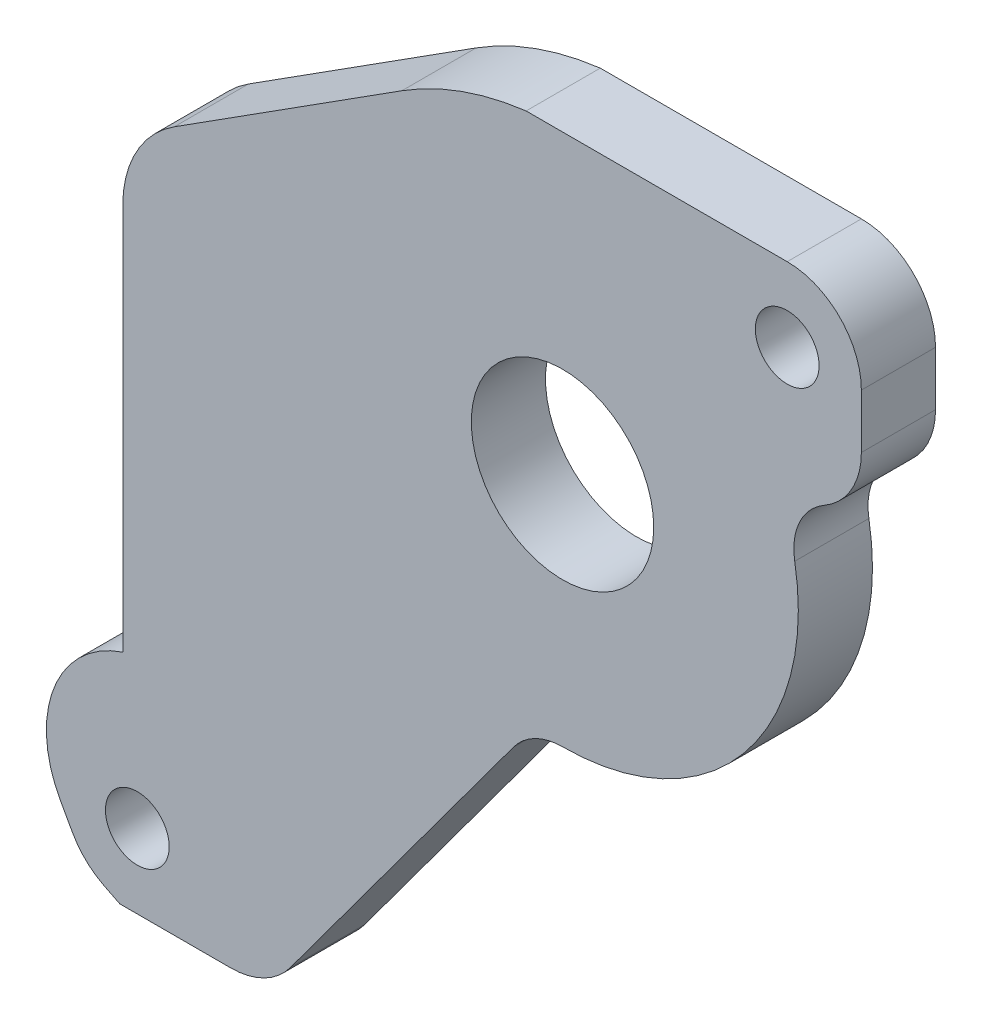
SolidWorks part; units mm, degrees
material "ﾎﾟﾘｴﾁﾚﾝｲﾐﾝ(PEI)"
ref_plane "正面" through (0, 0, 0) normal (0, 0, 1) x (1, 0, 0)
ref_plane "平面" through (0, 0, 0) normal (0, 1, 0) x (1, 0, 0)
ref_plane "右側面" through (0, 0, 0) normal (1, 0, 0) x (0, 0, -1)
sketch "ｽｹｯﾁ1" plane through (0, 0, 0) normal (0, 0, 1) x (1, 0, 0)
  line L0 (0, 24.75) -> (0, -24.75) construction
  line L1 (-5, 24.75) -> (5, 24.75) construction
  line L2 (-5, 24.75) -> (-5, -24.75) construction
  line L3 (-5, -24.75) -> (5, -24.75) construction
  line L4 (5, 24.75) -> (5, -24.75) construction
  line L5 (-5, 24.75) -> (5, -24.75) construction
  line L6 (-5, -24.75) -> (5, 24.75) construction
  line L7 (-5, 0) -> (5, 0) construction
  line L8 (0.65, -27.15) -> (0.65, -20.15)
  line L9 (-10.15, 20.15) -> (10.15, 20.15)
  line L10 (-10.15, 20.15) -> (-10.15, -20.15)
  line L11 (-10.15, -20.15) -> (10.15, -20.15)
  line L12 (10.15, 20.15) -> (10.15, -20.15)
  line L13 (-10.15, 20.15) -> (10.15, -20.15) construction
  line L14 (-10.15, -20.15) -> (10.15, 20.15) construction
  line L15 (-0.65, 27.15) -> (0.65, 27.15)
  line L16 (-0.65, 27.15) -> (-0.65, 20.15)
  line L17 (-0.65, 20.15) -> (0.65, 20.15)
  line L18 (0.65, 27.15) -> (0.65, 20.15)
  line L19 (-0.65, 27.15) -> (0.65, 20.15) construction
  line L20 (-0.65, 20.15) -> (0.65, 27.15) construction
  line L21 (-0.65, -27.15) -> (-0.65, -20.15)
  line L22 (-0.65, -27.15) -> (0.65, -27.15)
  line L23 (10.15, 0) -> (-51.75, 0) construction
  line L25 (-59.85, 30) -> (20.15, 30)
  line L26 (-59.85, 30) -> (-59.85, -30)
  line L27 (-59.85, -30) -> (20.15, -30)
  line L28 (20.15, 30) -> (20.15, -30)
  line L29 (-59.85, 30) -> (20.15, -30) construction
  line L30 (-59.85, -30) -> (20.15, 30) construction
  circle A0 centre (-5, 24.75) radius 2.15
  circle A1 centre (5, 24.75) radius 2.15
  circle A2 centre (5, -24.75) radius 2.15
  circle A3 centre (-5, -24.75) radius 2.15
  circle A4 centre (0, 10) radius 6.15
  point P0 (0, 0)
  point P14 (0, 0)
  point P19 (0, 23.65)
  point P29 (-19.85, 0)
  dimension "D3" = 4.3
  dimension "D11" = 12.3
  dimension "D1" = 10
  dimension "D2" = 49.5
  dimension "D4" = 20.3
  dimension "D5" = 40.3
  dimension "D6" = 1.3
  dimension "D7" = 7
  dimension "D8" = 60
  dimension "D9" = 10
  dimension "D10" = 80
  dimension "D12" = 20
extrude "ﾎﾞｽ - 押し出し1" add sketch "ｽｹｯﾁ1" along normal blind 5 contours L28 L25 L26 L27 A1 A0 L22 L21 L11 L10 L9 L16 L15 L18 L12 L8 A2 A3 | L12 L9 L10 L11 | A3 | L21 L22 L8 L11 | A2 | A0 | A1 | L18 L15 L16 L9 region at (0, -23.65, 0) region at (0, -1.6992, 0) region at (0, 23.65, 0) region at (-24.3956, 0, 0) region at (-5, 24.75, 0) region at (5, 24.75, 0) region at (5, -24.75, 0) region at (-5, -24.75, 0)
sketch "ｽｹｯﾁ2" plane through (0, 0, 5) normal (0, 0, 1) x (1, 0, 0)
  line L0 (-59.85, 0) -> (20.15, 0) construction
  line L1 (-59.85, 30) -> (-59.85, -30) construction
  line L2 (20.15, 30) -> (20.15, -30) construction
  line L3 (-54.85, 0) -> (-54.85, 10) construction
  line L4 (-54.85, 10) -> (-34.85, 10) construction
  circle A0 centre (-54.85, 10) radius 2.15
  circle A1 centre (-54.85, -10) radius 2.15
  circle A2 centre (-34.85, 10) radius 2.15
  circle A3 centre (-34.85, -10) radius 2.15
  dimension "D1" = 4.3
  dimension "D2" = 5
  dimension "D3" = 20
  dimension "D5" = 20
  dimension "D4" = 2
extrude "ｶｯﾄ - 押し出し1" cut sketch "ｽｹｯﾁ2" against normal through all
sketch "ｽｹｯﾁ3" plane through (0, 0, 5) normal (0, 0, 1) x (1, 0, 0)
  line L0 (-59.85, 30) -> (20.15, 30) construction
  line L1 (20.15, 30) -> (20.15, -30) construction
  line L6 (20.15, -30) -> (20.15, 30)
  line L7 (20.15, 30) -> (-59.85, 30)
  line L8 (-59.85, 30) -> (-59.85, -30)
  line L9 (-59.85, -30) -> (20.15, -30)
  line L10 (20.15, -30) -> (20.15, 30)
  line L11 (20.15, 30) -> (-59.85, 30)
  line L12 (-59.85, 30) -> (-59.85, -30)
  line L13 (-59.85, -30) -> (20.15, -30)
  circle A0 centre (15.15, 25) radius 5
  circle A1 centre (15.15, 25) radius 2.15
  line M12 (20.15, 30) -> (-59.85, 30)
  dimension "D1" = 10
  dimension "D2" = 4.3
  dimension "D3" = 0
extrude "ｶｯﾄ - 押し出し2" cut sketch "ｽｹｯﾁ3" against normal through all contours A1 | A0 L10 M12 region at (19.0332, 28.8832, 5) region at (15.15, 25, 5)
sketch "ｽｹｯﾁ4" plane through (0, 0, 5) normal (0, 0, 1) x (1, 0, 0)
  line L0 (-59.85, 0) -> (20.15, 0) construction
  line L1 (-59.85, 30) -> (-59.85, -30) construction
  line L2 (20.15, 25) -> (20.15, -30) construction
  line L3 (-59.85, 15) -> (-29.85, 30)
  line L4 (-59.85, 30) -> (15.15, 30) construction
  line L5 (-59.85, -15) -> (-29.85, -30)
  line L6 (12.0657, -6.1382) -> (-19.85, -30)
  line L10 (20.15, -30) -> (20.15, 25)
  line L11 (15.15, 30) -> (-59.85, 30)
  line L12 (-59.85, 30) -> (-59.85, -30)
  line L13 (-59.85, -30) -> (20.15, -30)
  line L14 (20.15, -30) -> (20.15, 25)
  line L15 (15.15, 30) -> (-59.85, 30)
  line L16 (-59.85, 30) -> (-59.85, -30)
  line L17 (-59.85, -30) -> (20.15, -30)
  circle A0 centre (0, 10) radius 6.15 construction
  arc A1 (20.15, 25) -> (15.15, 30) centre (15.15, 25) ccw
  arc A2 (20.15, 25) -> (15.15, 30) centre (15.15, 25) ccw
  circle A3 centre (0, 10) radius 6.15
  circle A4 centre (0, 10) radius 20.15
  line M15 (20.15, -30) -> (20.15, 25)
  line M17 (15.15, 30) -> (-59.85, 30)
  line M18 (-59.85, 30) -> (-59.85, -30)
  line M19 (-59.85, -30) -> (20.15, -30)
  dimension "D4" = 40
  dimension "D1" = 30
  dimension "D2" = 30
  dimension "D3" = 0
extrude "ｶｯﾄ - 押し出し3" cut sketch "ｽｹｯﾁ4" against normal through all contours L3 M18 M17 | L5 M18 M19 | L0 A4 L6 M19 M15 | A4 L0 L14 region at (-49.85, 25, 5) region at (-49.85, -25, 5) region at (19.3629, 2.4658, 5) region at (6.9241, -19.8416, 5)
sketch "ｽｹｯﾁ6" plane through (0, 0, 5) normal (0, 0, 1) x (1, 0, 0)
  line L0 (-59.85, -15) -> (-29.85, -30) construction
  line L1 (-29.85, -30) -> (-19.85, -30) construction
  circle A0 centre (-28.6697, -25) radius 5 construction
  circle A1 centre (-28.6697, -25) radius 2.15
  dimension "D1" = 10
  dimension "D2" = 4.3
extrude "ｶｯﾄ - 押し出し5" cut sketch "ｽｹｯﾁ6" against normal through all
sketch "ｽｹｯﾁ7" plane through (0, 0, 5) normal (0, 0, 1) x (1, 0, 0)
  line L0 (-39.85, -15.2) -> (-33.038, -27.4326)
  line L1 (-34.85, 10) -> (-34.85, -10) construction
  line L2 (-39.85, -15.2) -> (-29.65, -15.2)
  line L3 (-39.85, 15) -> (-29.85, 15) construction
  line L4 (-39.85, 15) -> (-39.85, -15) construction
  line L5 (-39.85, -15) -> (-29.85, -15) construction
  line L6 (-29.85, 15) -> (-29.85, -15) construction
  line L7 (-39.85, 15) -> (-29.85, -15) construction
  line L8 (-39.85, -15) -> (-29.85, 15) construction
  line L9 (-29.65, 15) -> (-29.65, -15.2)
  line L10 (-29.65, 15) -> (-10.8282, 26.9933)
  line L17 (-29.85, 30) -> (-59.85, 15)
  line L18 (-59.85, 15) -> (-59.85, -15)
  line L19 (-59.85, -15) -> (-29.85, -30)
  line L20 (-29.85, -30) -> (-19.85, -30)
  line L21 (-19.85, -30) -> (12.0657, -6.1382)
  line L22 (20.15, 10) -> (20.15, 25)
  line L23 (15.15, 30) -> (-29.85, 30)
  line L24 (-29.85, 30) -> (-59.85, 15)
  line L25 (-59.85, 15) -> (-59.85, -15)
  line L26 (-59.85, -15) -> (-29.85, -30)
  line L27 (-29.85, -30) -> (-19.85, -30)
  line L28 (-19.85, -30) -> (12.0657, -6.1382)
  line L29 (20.15, 10) -> (20.15, 25)
  line L30 (15.15, 30) -> (-29.85, 30)
  circle A1 centre (-34.85, -10) radius 2.15 construction
  circle A2 centre (15.15, 25) radius 5
  arc A3 (20.15, 25) -> (15.15, 30) centre (15.15, 25) ccw construction
  circle A4 centre (-28.6697, -25) radius 5
  circle A5 centre (0, 10) radius 20.15
  arc A6 (12.0657, -6.1382) -> (20.15, 10) centre (0, 10) ccw
  arc A7 (20.15, 25) -> (15.15, 30) centre (15.15, 25) ccw
  arc A8 (12.0657, -6.1382) -> (20.15, 10) centre (0, 10) ccw
  arc A9 (20.15, 25) -> (15.15, 30) centre (15.15, 25) ccw
  circle A10 centre (-28.6697, -25) radius 2.15 construction
  point P11 (-34.85, 0)
  dimension "D1" = 10
  dimension "D4" = 0
  dimension "D2" = 30
  dimension "D3" = 0.2
extrude "ｶｯﾄ - 押し出し7" cut sketch "ｽｹｯﾁ7" against normal through all contours A5 L1 L27 L28 A8 A4 L0 L2 L9 L10 L7 L17 L8 region at (-41.0194, 4.3602, 5)
fillet "ﾌｨﾚｯﾄ1" radius 7.5 2 edges at (-39.85, -15.2, 2.5) (-29.65, 15, 2.5)
sketch "ｽｹｯﾁ8" plane through (0, 0, 5) normal (0, 0, 1) x (1, 0, 0)
  line L0 (19.6962, 13.473) -> (0, 10) construction
  line L1 (0, -10) -> (0, 10) construction
  line L2 (-19.85, -30) -> (-3.2993, -7.5659)
  circle A0 centre (0, 10) radius 6.15 construction
  circle A1 centre (0, 10) radius 6.15
  arc A2 (19.6962, 13.473) -> (0, -10) centre (0, 10) cw construction
  arc A3 (0, -14.1) -> (23.7339, 14.1849) centre (0, 10) ccw
  arc A4 (0, -5.9) -> (15.6584, 12.761) centre (0, 10) ccw
  arc A5 (0, -5.9) -> (0, -14.1) centre (0, -10) ccw
  arc A6 (23.7339, 14.1849) -> (15.6584, 12.761) centre (19.6962, 13.473) ccw
  point P5 (15.3209, -2.8558)
  line M12 (-19.85, -30) -> (12.0657, -6.1382)
  arc M13 (12.0657, -6.1382) -> (20.15, 10) centre (0, 10) ccw
  line M14 (20.15, 10) -> (20.15, 25)
  dimension "D1" = 20
  dimension "D2" = 8.2
  dimension "D3" = 100
extrude "ｶｯﾄ - 押し出し8" cut sketch "ｽｹｯﾁ8" against normal through all contours A5 L2 A3 M12 | A6 A4 A5 A3 M14 M12 M13 region at (-8.2005, -18.2687, 5) region at (-1.6682, -6.6962, 5)
fillet "ﾌｨﾚｯﾄ2" radius 5 1 edges at (-19.85, -30, 2.5)
fillet "ﾌｨﾚｯﾄ3" radius 5 1 edges at (20.15, 17.5478, 2.5)
